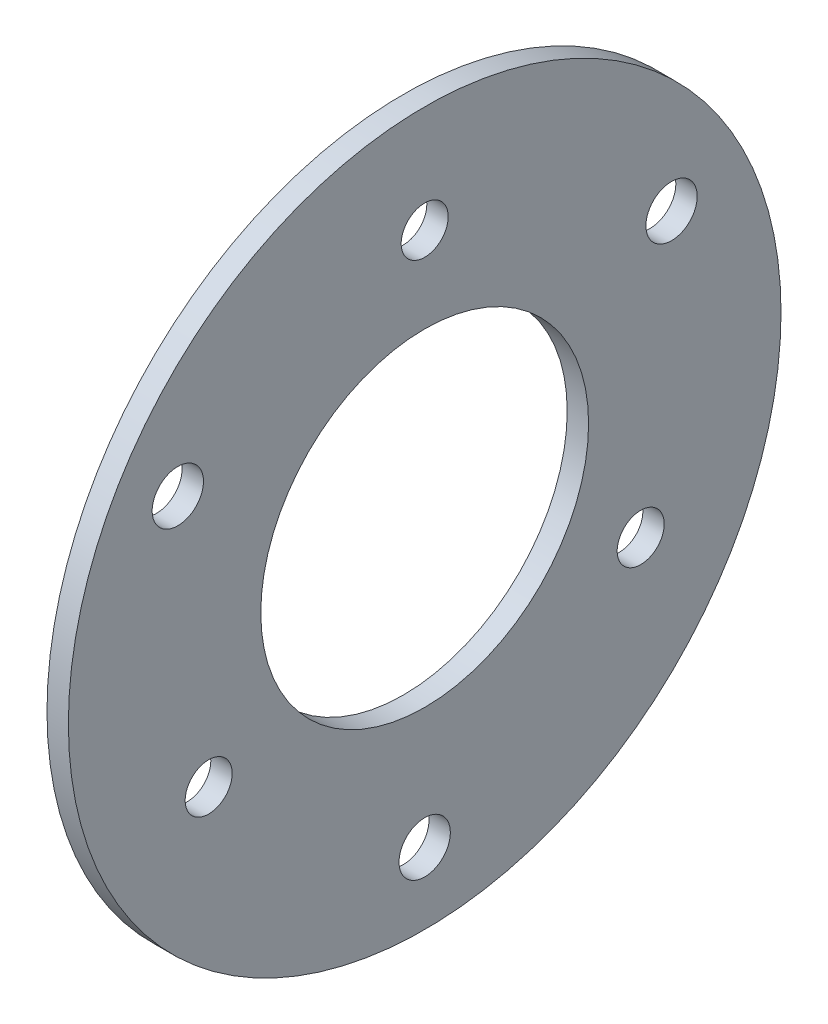
SolidWorks part; units mm, degrees
material "1023 Arkusz stali węglowej (SS)"
ref_plane "Płaszczyzna przednia" through (0, 0, 0) normal (0, 0, 1) x (1, 0, 0)
ref_plane "Płaszczyzna górna" through (0, 0, 0) normal (0, 1, 0) x (1, 0, 0)
ref_plane "Płaszczyzna prawa" through (0, 0, 0) normal (1, 0, 0) x (0, 0, -1)
sketch "Szkic1" plane through (0, 0, 0) normal (1, 0, 0) x (0, 0, -1)
  circle A0 centre (0, 0) radius 50
  circle A1 centre (0, 0) radius 23
  circle A2 centre (0, 35) radius 3.3
  circle A3 centre (30.3109, -17.5) radius 3.3
  circle A4 centre (-30.3109, -17.5) radius 3.3
  circle A5 centre (0, -40) radius 3.6
  circle A6 centre (-34.641, 20) radius 3.6
  circle A7 centre (34.641, 20) radius 3.6
  point P12 (0, 0)
  point P19 (0, 0)
  dimension "D1" = 100
  dimension "D3" = 6.6
  dimension "D4" = 46
  dimension "D6" = 7.2
  dimension "D2" = 35
  dimension "D7" = 40
  dimension "D5" = 3
  dimension "D8" = 3
extrude "Dodanie-wyciągnięcie1" add sketch "Szkic1" along normal blind 3
